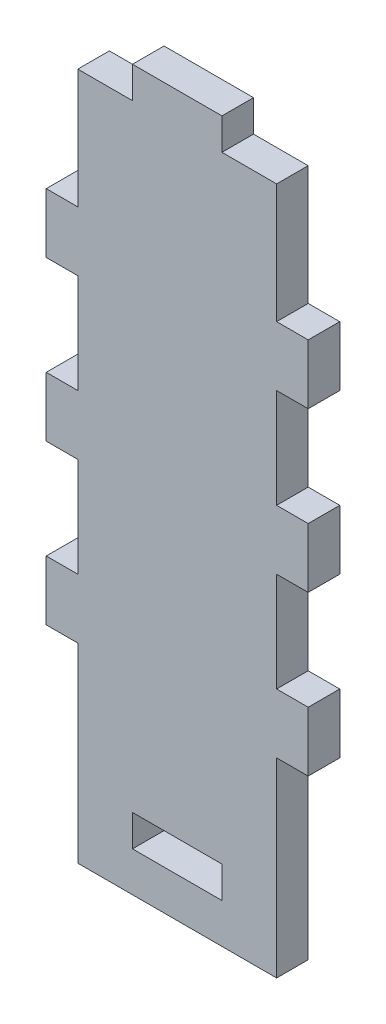
SolidWorks part; units mm, degrees
ref_plane "Front Plane" through (0, 0, 0) normal (0, 0, 1) x (1, 0, 0)
ref_plane "Top Plane" through (0, 0, 0) normal (0, 1, 0) x (1, 0, 0)
ref_plane "Right Plane" through (0, 0, 0) normal (1, 0, 0) x (0, 0, -1)
sketch "Sketch1" plane through (0, 0, 0) normal (0, 0, 1) x (1, 0, 0)
  line L0 (-5.5, 7.175) -> (0, 7.175) construction
  line L1 (0, 19.175) -> (3.175, 19.175)
  line L2 (3.175, 19.175) -> (3.175, 25.175)
  line L3 (3.175, 25.175) -> (0, 25.175)
  line L4 (0, 25.175) -> (0, 35.175)
  line L5 (0, 35.175) -> (3.175, 35.175)
  line L6 (3.175, 35.175) -> (3.175, 41.175)
  line L7 (3.175, 41.175) -> (0, 41.175)
  line L8 (0, 41.175) -> (0, 51.175)
  line L9 (0, 51.175) -> (3.175, 51.175)
  line L10 (3.175, 51.175) -> (3.175, 57.175)
  line L11 (3.175, 57.175) -> (0, 57.175)
  line L12 (0, 57.175) -> (0, 69.175)
  line L13 (0, 69.175) -> (-5.5, 69.175)
  line L14 (-5.5, 69.175) -> (-5.5, 72.35)
  line L15 (-5.5, 72.35) -> (-14.5, 72.35)
  line L16 (-14.5, 72.35) -> (-14.5, 69.175)
  line L17 (-14.5, 69.175) -> (-20, 69.175)
  line L18 (3.175, 34.5875) -> (-38.4558, 34.5875) construction
  line L19 (-10, 61.175) -> (-10, 29) construction
  line L20 (-20, 57.175) -> (-20, 69.175)
  line L21 (-23.175, 57.175) -> (-20, 57.175)
  line L22 (-23.175, 51.175) -> (-23.175, 57.175)
  line L23 (-20, 51.175) -> (-23.175, 51.175)
  line L24 (-20, 41.175) -> (-20, 51.175)
  line L25 (-23.175, 41.175) -> (-20, 41.175)
  line L26 (-23.175, 35.175) -> (-23.175, 41.175)
  line L27 (-20, 35.175) -> (-23.175, 35.175)
  line L28 (-20, 25.175) -> (-20, 35.175)
  line L29 (-23.175, 25.175) -> (-20, 25.175)
  line L30 (-23.175, 19.175) -> (-23.175, 25.175)
  line L31 (-20, 19.175) -> (-23.175, 19.175)
  line L32 (-14.5, 7.175) -> (-20, 7.175) construction
  line L33 (-20, 0) -> (0, 0)
  line L34 (-10, 0) -> (-10, 4)
  line L35 (-5.5, 4) -> (-5.5, 7.175)
  line L36 (-5.5, 7.175) -> (-14.5, 7.175)
  line L37 (-5.5, 4) -> (-14.5, 4)
  line L38 (-14.5, 4) -> (-14.5, 7.175)
  line L39 (-20, 7.175) -> (-20, 19.175)
  line L40 (-20, 7.175) -> (-20, 0)
  line L41 (0, 7.175) -> (0, 19.175)
  line L42 (0, 7.175) -> (0, 0)
  point P44 (-10, 7.175)
  dimension "D1" = 4
  dimension "D2" = 3.175
  dimension "D3" = 6
  dimension "D4" = 10
  dimension "D5" = 9
  dimension "D6" = 3.175
  dimension "D7" = 20
  dimension "D8" = 3.175
  dimension "D9" = 9
  dimension "D10" = 62
extrude "Boss-Extrude2" add sketch "Sketch1" along normal mid plane 3.175 contours L36 L35 L37 L33 L1 L2 L3 L4 L5 L6 L7 L8 L9 L10 L11 L12 L13 L14 L15 L16 L17 L20 L21 L22 L23 L24 L25 L26 L27 L28 L29 L30 L31 L38 region at (-10, 36.1047, 0)
